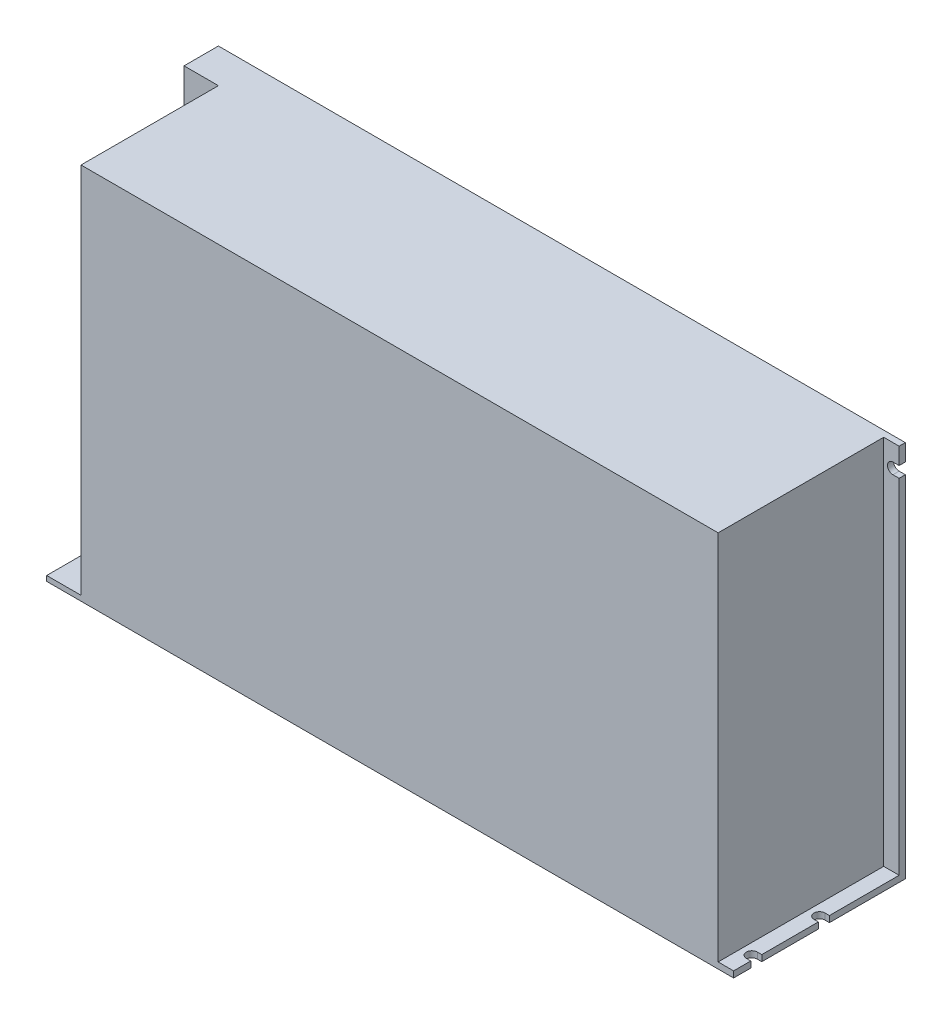
SolidWorks part; units mm, degrees
ref_plane "前视基准面" through (0, 0, 0) normal (0, 0, 1) x (1, 0, 0)
ref_plane "上视基准面" through (0, 0, 0) normal (0, 1, 0) x (1, 0, 0)
ref_plane "右视基准面" through (0, 0, 0) normal (1, 0, 0) x (0, 0, -1)
sketch "草图1" plane through (0, 0, 0) normal (0, 0, 1) x (1, 0, 0)
  line L1 (-122.0332, 60.8421) -> (77.9668, 60.8421)
  line L2 (-122.0332, 60.8421) -> (-122.0332, -49.1579)
  line L3 (-122.0332, -49.1579) -> (77.9668, -49.1579)
  line L4 (77.9668, 60.8421) -> (77.9668, -49.1579)
  dimension "D1" = 110
  dimension "D2" = 200
extrude "拉伸1" add sketch "草图1" along normal blind 50
sketch "草图2" plane through (0, 0, 0) normal (0, 0, 1) x (1, 0, 0)
  line L2 (-60.5332, -45.7596) -> (-60.5332, 72.1566) construction
  line L3 (-80.4338, -34.1579) -> (70.1504, -34.1579) construction
  line L4 (65.4668, -41.7166) -> (65.4668, 56.9614) construction
  line L5 (70.1504, 50.8421) -> (-80.4338, 50.8421) construction
  line L6 (-122.0332, -49.1579) -> (77.9668, -49.1579) construction
  line L7 (-122.0332, 60.8421) -> (-122.0332, -49.1579) construction
  circle A0 centre (-60.5332, 50.8421) radius 2
  circle A1 centre (65.4668, 50.8421) radius 2
  circle A2 centre (-60.5332, -34.1579) radius 2
  circle A3 centre (65.4668, -34.1579) radius 2
  dimension "D2" = 126
  dimension "D3" = 85
  dimension "D4" = 4
  dimension "D5" = 4
  dimension "D6" = 4
  dimension "D7" = 4
  dimension "D9" = 15
  dimension "D10" = 61.5
extrude "切除-拉伸1" cut sketch "草图2" along normal blind 10
sketch "草图3" plane through (0, 0, 50) normal (0, 0, 1) x (1, 0, 0)
  line L1 (-122.0332, -49.1579) -> (77.9668, -49.1579) construction
  line L2 (-122.0332, 60.8421) -> (-112.0332, 60.8421)
  line L3 (-122.0332, 60.8421) -> (-122.0332, -47.6579)
  line L4 (-122.0332, -47.6579) -> (-112.0332, -47.6579)
  line L6 (-112.0332, 60.8421) -> (-112.0332, -47.6579)
  dimension "D1" = 10
  dimension "D2" = 1.5
extrude "切除-拉伸2" cut sketch "草图3" against normal blind 40
sketch "草图6" plane through (0, 60.8421, 0) normal (0, 1, 0) x (-1, 0, 0)
  line L0 (-77.9668, 0) -> (122.0332, 0) construction
  line L1 (-77.9668, 50) -> (-73.4668, 50)
  line L2 (-77.9668, 50) -> (-77.9668, 1.8)
  line L3 (-77.9668, 1.8) -> (-73.4668, 1.8)
  line L4 (-73.4668, 50) -> (-73.4668, 1.8)
  dimension "D1" = 1.8
  dimension "D2" = 4.5
extrude "切除-拉伸5" cut sketch "草图6" against normal offset from surface (108.2 mm away) 1.8 up to face at (-22.0332, -49.1579, 25)
sketch "草图4" plane through (0, -49.1579, 0) normal (0, -1, 0) x (1, 0, 0)
  line L0 (94.9806, 13) -> (-156.73, 13) construction
  line L2 (-122.0332, 0) -> (77.9668, 0) construction
  line L3 (-116.0332, -14.188) -> (-116.0332, 56.6156) construction
  line L4 (56.9668, -14.188) -> (56.9668, 66.81) construction
  line L5 (77.9668, 50) -> (77.9668, 0) construction
  line L7 (67.1757, 38) -> (-119.4663, 38) construction
  circle A0 centre (-116.0332, 13) radius 1.5
  circle A1 centre (56.9668, 13) radius 1.5
  circle A2 centre (56.9668, 38) radius 1.5
  dimension "D3" = 3
  dimension "D4" = 3
  dimension "D5" = 21
  dimension "D6" = 3
  dimension "D1" = 13
  dimension "D2" = 173
  dimension "D7" = 25
extrude "切除-拉伸3" cut sketch "草图4" against normal blind 10
sketch "草图5" plane through (0, -49.1579, 0) normal (0, -1, 0) x (1, 0, 0)
  line L0 (-126.2446, 33) -> (-113.68, 33) construction
  line L1 (-116.0332, 38.2624) -> (-116.0332, 28.9624) construction
  line L2 (77.9668, 45) -> (77.9668, 41.8)
  line L3 (-122.0332, 0) -> (77.9668, 0) construction
  line L4 (-122.0332, 50) -> (-122.0332, 0) construction
  line L5 (87.4781, 33.55) -> (60.2345, 33.55) construction
  line L6 (77.9668, 45) -> (76.6668, 45)
  line L7 (77.9668, 50) -> (77.9668, 0) construction
  line L8 (77.9668, 41.8) -> (76.6668, 41.8)
  line L9 (76.6668, 41.8241) -> (76.6668, 47.3634) construction
  line L10 (78.6478, 43.4) -> (74.1624, 43.4) construction
  line L11 (-122.0332, 50) -> (77.9668, 50) construction
  line L12 (77.9668, 22.1) -> (76.6668, 22.1)
  line L13 (77.9668, 25.3) -> (76.6668, 25.3)
  line L14 (77.9668, 22.1) -> (77.9668, 25.3)
  circle A0 centre (-116.0332, 33) radius 1.6
  arc A1 (76.6668, 45) -> (76.6668, 41.8) centre (76.6668, 43.4) ccw
  arc A2 (76.6668, 22.1) -> (76.6668, 25.3) centre (76.6668, 23.7) cw
  dimension "D3" = 3.2
  dimension "D1" = 33
  dimension "D2" = 6
  dimension "D4" = 3.2
  dimension "D5" = 1.3
  dimension "D6" = 5
  dimension "D7" = 16.5
extrude "切除-拉伸4" cut sketch "草图5" against normal blind 10
sketch "草图7" plane through (0, 0, 10) normal (0, 0, 1) x (1, 0, 0)
  line L0 (-122.0332, 60.8421) -> (-122.0332, -47.6579) construction
  line L1 (-112.0332, -47.6579) -> (-122.0332, -47.6579)
  line L2 (-112.0332, -47.6579) -> (-112.0332, -37.6579)
  line L3 (-112.0332, -37.6579) -> (-122.0332, -37.6579)
  line L4 (-122.0332, -47.6579) -> (-122.0332, -37.6579)
  line L5 (-112.0332, 60.8421) -> (-122.0332, 60.8421) construction
  dimension "D1" = 98.5
extrude "切除-拉伸6" cut sketch "草图7" against normal offset from surface (8.2 mm away) 1.8 up to face at (-58.5332, -34.1579, 0)
sketch "草图8" plane through (0, 0, 0) normal (0, 0, -1) x (-1, 0, 0)
  line L0 (-80.5775, 54.3421) -> (-67.3957, 54.3421) construction
  line L1 (-76.1668, 59.3745) -> (-76.1668, 52.6163) construction
  line L2 (-77.9668, 55.9421) -> (-76.1668, 55.9421)
  line L3 (-77.9668, -49.1579) -> (-77.9668, 60.8421) construction
  line L4 (-77.9668, 52.7421) -> (-76.1668, 52.7421)
  line L5 (-77.9668, 60.8421) -> (122.0332, 60.8421) construction
  line L6 (114.9432, -41.1579) -> (126.7753, -41.1579) construction
  line L8 (118.5332, -38.262) -> (118.5332, -48.1083) construction
  line L9 (122.0332, -49.1579) -> (-77.9668, -49.1579) construction
  line L10 (122.0332, 60.8421) -> (122.0332, -49.1579) construction
  line L11 (-77.9668, 55.9421) -> (-77.9668, 52.7421)
  arc A0 (-76.1668, 55.9421) -> (-76.1668, 52.7421) centre (-76.1668, 54.3421) cw
  circle A1 centre (118.5332, -41.1579) radius 1.6
  dimension "D3" = 6.5
  dimension "D4" = 3.2
  dimension "D1" = 3.2
  dimension "D2" = 1.8
  dimension "D5" = 8
  dimension "D6" = 3.5
extrude "切除-拉伸7" cut sketch "草图8" against normal blind 1.8
